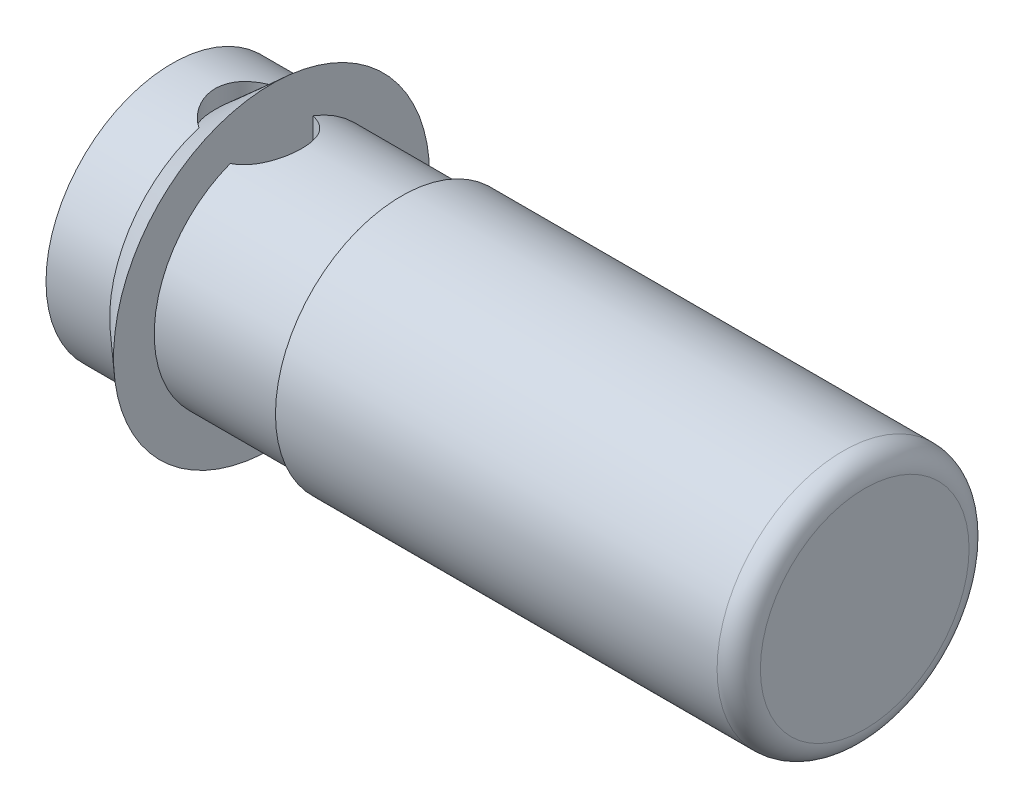
SolidWorks part; units mm, degrees
ref_plane "Front Plane" through (0, 0, 0) normal (0, 0, 1) x (1, 0, 0)
ref_plane "Top Plane" through (0, 0, 0) normal (0, 1, 0) x (1, 0, 0)
ref_plane "Right Plane" through (0, 0, 0) normal (1, 0, 0) x (0, 0, -1)
sketch "Sketch2" plane through (0, 0, 0) normal (1, 0, 0) x (0, 0, -1)
  circle A0 centre (0, 0) radius 1.455
  dimension "D1" = 2.91
extrude "Boss-Extrude3" add sketch "Sketch2" along normal blind 6 contours A0
sketch "Sketch3" plane through (6, 0, 0) normal (1, 0, 0) x (0, 0, -1)
  circle A0 centre (0, 0) radius 2.5
  dimension "D1" = 5
extrude "Boss-Extrude4" add sketch "Sketch3" along normal blind 3
sketch "Sketch4" plane through (0, 0, 0) normal (0, 1, 0) x (1, 0, 0)
  circle A0 centre (1, 0) radius 0.5
  dimension "D1" = 1
  dimension "D2" = 1
extrude "Cut-Extrude1" cut sketch "Sketch4" against normal through all both and the other way through all
ref_axis "Axis2" through (1, -1.455, 0) along (0, 1, 0)
ref_plane "Plane1" through (1, 0, 0) normal (1, 0, 0) x (0, 1, 0)
sketch "Sketch6" plane through (1, 0, 0) normal (1, 0, 0) x (0, 1, 0)
  circle A0 centre (0, 0) radius 1.575
  dimension "D1" = 3.15
extrude "Boss-Extrude5" add sketch "Sketch6" along normal blind 0.15
sketch "Sketch7" plane through (0, 0, 0) normal (0, 0, 1) x (1, 0, 0)
  line L0 (1.15, 1.825) -> (0, 0.8)
  line L1 (0, 0.8) -> (1.15, 0.8)
  line L2 (1.15, 0.8) -> (1.15, 1.825)
  dimension "D1" = 0
  dimension "D2" = 0
  dimension "D3" = 0.25
  dimension "D4" = 0.8
  dimension "D5" = 0
ref_axis "Axis1" through (9.45, 0, 0) along (-1, 0, 0)
revolve "Revolve1" add sketch "Sketch7" angle 360 about axis through (9.45, 0, 0) along (-1, 0, 0)
sketch "Sketch9" plane through (9, 0, 0) normal (1, 0, 0) x (0, 0, -1)
  circle A0 centre (0, 0) radius 2.5
  circle A1 centre (0, 0) radius 1.455
  circle A2 centre (0, 0) radius 1.455 construction
  dimension "D1" = 0
extrude "Cut-Extrude3" cut sketch "Sketch9" against normal up to next
sketch "Sketch10" plane through (9, 0, 0) normal (1, 0, 0) x (0, 0, -1)
  circle A0 centre (0, 0) radius 1.455
extrude "Cut-Extrude4" cut sketch "Sketch10" against normal blind 1
fillet "Fillet1" radius 0.25 1 edges at (8, 0, -1.455)
sketch "Sketch11" plane through (1.15, 0, 0) normal (1, 0, 0) x (0, 0, -1)
  circle A0 centre (0, 0) radius 1.355
  arc A1 (0.477, -1.3746) -> (0.477, 1.3746) centre (0, 0) ccw construction
  circle A2 centre (0, 0) radius 1.455
  dimension "D1" = 0.1
extrude "Cut-Extrude5" cut sketch "Sketch11" along normal blind 1.5
